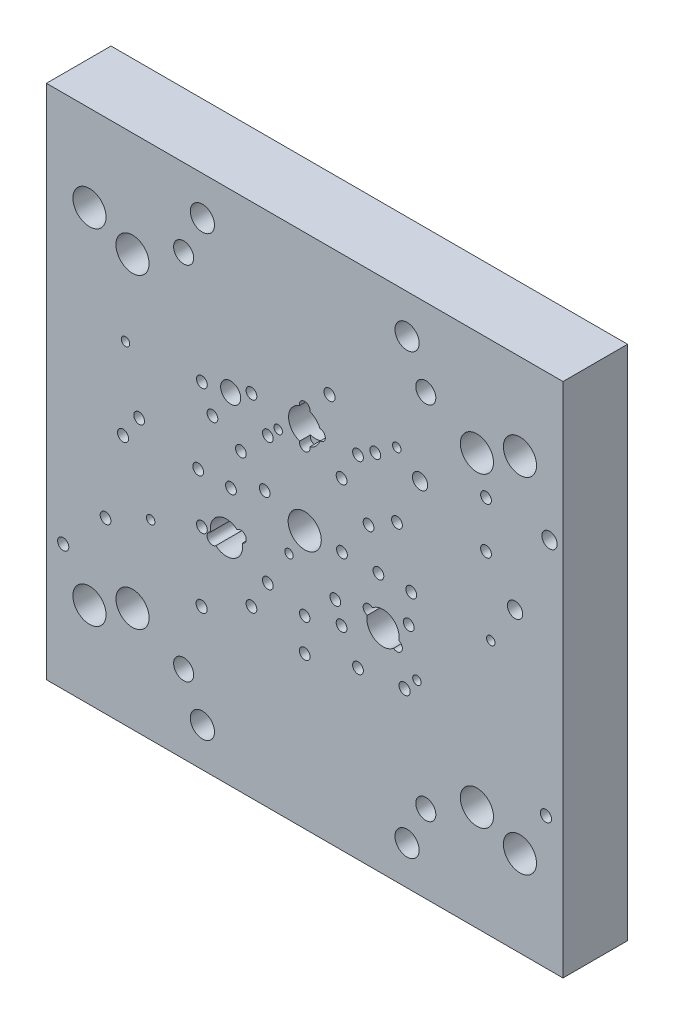
SolidWorks part; units mm, degrees
ref_plane "Front Plane" through (0, 0, 0) normal (0, 0, 1) x (1, 0, 0)
ref_plane "Top Plane" through (0, 0, 0) normal (0, 1, 0) x (1, 0, 0)
ref_plane "Right Plane" through (0, 0, 0) normal (1, 0, 0) x (0, 0, -1)
sketch "Sketch1" plane through (0, 0, 0) normal (0, 0, 1) x (1, 0, 0)
  line L1 (-152.4, 152.4) -> (152.4, 152.4)
  line L2 (-152.4, 152.4) -> (-152.4, -152.4)
  line L3 (-152.4, -152.4) -> (152.4, -152.4)
  line L4 (152.4, 152.4) -> (152.4, -152.4)
  line L5 (-152.4, 152.4) -> (152.4, -152.4) construction
  line L6 (-152.4, -152.4) -> (152.4, 152.4) construction
  point P0 (0, 0)
  dimension "D1" = 304.8
  dimension "D2" = 304.8
extrude "Boss-Extrude1" add sketch "Sketch1" along normal blind 38.1
sketch "Sketch2" plane through (0, 0, 38.1) normal (0, 0, 1) x (1, 0, 0)
  line L0 (-152.4, 0) -> (152.4, 0) construction
  line L5 (-152.4, 152.4) -> (-152.4, -152.4) construction
  line L6 (152.4, -152.4) -> (152.4, 152.4) construction
  line L7 (-152.4, -101.6) -> (152.4, -101.6) construction
  line L8 (-152.4, 101.6) -> (152.4, 101.6) construction
  line L9 (0, 101.6) -> (0, -101.6) construction
  line L10 (127, 101.6) -> (127, -101.6) construction
  line L11 (-127, 101.6) -> (-127, -101.6) construction
  circle A0 centre (-127, 101.6) radius 6.5151
  circle A1 centre (127, 101.6) radius 6.5151
  circle A2 centre (127, -101.6) radius 6.5151
  circle A3 centre (-127, -101.6) radius 6.5151
  circle A4 centre (0, 0) radius 6.5151
  dimension "D5" = 13.0302
  dimension "D1" = 101.6
  dimension "D2" = 101.6
  dimension "D3" = 127
  dimension "D4" = 127
extrude "HAAS T-Slot Holes" cut sketch "Sketch2" against normal through all
sketch "Sketch3" plane through (0, 0, 38.1) normal (0, 0, 1) x (1, 0, 0)
  circle A0 centre (-127, 101.6) radius 9.779
  circle A1 centre (127, 101.6) radius 9.779
  circle A2 centre (0, 0) radius 9.779
  circle A3 centre (127, -101.6) radius 9.779
  circle A4 centre (-127, -101.6) radius 9.779
  dimension "D1" = 19.558
extrude "HAAS Counter Bores" cut sketch "Sketch3" against normal offset from surface (22.225 mm away) 15.875 contours A0 | A1 | A2 | A3 | A4 up to face at (6.5151, 0, 0)
sketch "Sketch4" plane through (0, 0, 38.1) normal (0, 0, 1) x (1, 0, 0)
  line L0 (-127, 90.4875) -> (127, 90.4875) construction
  line L1 (-127, 30.1625) -> (127, 30.1625) construction
  line L2 (-127, 30.1625) -> (-127, -30.1625) construction
  line L3 (-127, -30.1625) -> (127, -30.1625) construction
  line L4 (127, 30.1625) -> (127, -30.1625) construction
  line L5 (-127, 30.1625) -> (127, -30.1625) construction
  line L6 (-127, -30.1625) -> (127, 30.1625) construction
  line L7 (-127, -90.4875) -> (127, -90.4875) construction
  line L8 (-101.6, 90.4875) -> (-101.6, 84.1375) construction
  line L9 (-101.6, -90.4875) -> (-101.6, -84.1375) construction
  line L10 (101.6, -90.4875) -> (101.6, -84.1375) construction
  line L11 (101.6, 90.4875) -> (101.6, 84.1375) construction
  circle A0 centre (-101.6, 90.4875) radius 6.5151
  circle A1 centre (101.6, 90.4875) radius 6.5151
  circle A2 centre (-101.6, -90.4875) radius 6.5151
  circle A3 centre (101.6, -90.4875) radius 6.5151
  point P0 (0, 0)
  dimension "D9" = 13.0302
  dimension "D1" = 60.325
  dimension "D2" = 254
  dimension "D5" = 203.2
  dimension "D6" = 25.4
  dimension "D7" = 203.2
  dimension "D8" = 6.35
  dimension "D3" = 60.325
  dimension "D4" = 60.325
extrude "Tormach T-Slot Holes" cut sketch "Sketch4" against normal through all
sketch "Sketch5" plane through (0, 0, 38.1) normal (0, 0, 1) x (1, 0, 0)
  circle A0 centre (-101.6, 90.4875) radius 9.779
  circle A1 centre (101.6, 90.4875) radius 9.779
  circle A2 centre (101.6, -90.4875) radius 9.779
  circle A3 centre (-101.6, -90.4875) radius 9.779
  dimension "D1" = 19.558
extrude "Tormach Counter bores" cut sketch "Sketch5" against normal up to surface (22.225 mm away) up to face at (-117.221, 101.6, 15.875)
sketch "Sketch6" plane through (0, 0, 38.1) normal (0, 0, 1) x (1, 0, 0)
  circle A0 centre (0, 0) radius 43.5 construction
  circle A1 centre (0, 43.5) radius 3.0734
  circle A2 centre (0, -43.5) radius 3.0734
  dimension "D1" = 87.0001
  dimension "D2" = 6.1468
extrude "Sprocket Locating Holes" cut sketch "Sketch6" against normal blind 6.35
sketch "Sketch7" plane through (0, 0, 38.1) normal (0, 0, 1) x (1, 0, 0)
  circle A0 centre (0, 0) radius 43.5 construction
  circle A2 centre (43.5, 0) radius 3.175
  circle A4 centre (37.6721, -21.75) radius 3.175
  circle A5 centre (21.75, -37.6721) radius 3.175
  circle A6 centre (0, -43.5) radius 3.175 [skipped]
  circle A7 centre (-21.75, -37.6721) radius 3.175
  circle A8 centre (-37.6721, -21.75) radius 3.175
  circle A9 centre (-43.5, 0) radius 3.175
  circle A10 centre (-37.6721, 21.75) radius 3.175
  circle A11 centre (-21.75, 37.6721) radius 3.175
  circle A12 centre (0, 43.5) radius 3.175 [skipped]
  circle A13 centre (21.75, 37.6721) radius 3.175
  circle A14 centre (37.6721, 21.75) radius 3.175
  point P31 (0, 0)
  dimension "D1" = 87.0001
  dimension "D2" = 6.35
  dimension "D3" = 12
extrude "Sprocket Mounting clearance holes" cut sketch "Sketch7" against normal blind 9.525
sketch "Sketch8" plane through (0, 0, 38.1) normal (0, 0, 1) x (1, 0, 0)
  line L1 (-71.4375, 106.4641) -> (71.4375, 106.4641) construction
  line L2 (-71.4375, 106.4641) -> (-71.4375, -106.4641) construction
  line L3 (-71.4375, -106.4641) -> (71.4375, -106.4641) construction
  line L4 (71.4375, 106.4641) -> (71.4375, -106.4641) construction
  line L5 (-71.4375, 106.4641) -> (71.4375, -106.4641) construction
  line L6 (-71.4375, -106.4641) -> (71.4375, 106.4641) construction
  circle A0 centre (-71.4375, 106.4641) radius 5.9182
  circle A1 centre (71.4375, 106.4641) radius 5.9182
  circle A2 centre (71.4375, -106.4641) radius 5.9182
  circle A3 centre (-71.4375, -106.4641) radius 5.9182
  point P0 (0, 0)
  dimension "D3" = 11.8364
  dimension "D1" = 142.875
  dimension "D2" = 212.9282
extrude "1/2-13 Tapped Holes" cut sketch "Sketch8" against normal blind 19.05
sketch "Sketch9" plane through (0, 0, 38.1) normal (0, 0, 1) x (1, 0, 0)
  circle A0 centre (-117.5189, -52.2876) radius 3.175
  circle A1 centre (-60.6634, -28.4101) radius 3.175
  circle A2 centre (-60.6634, 45.677) radius 3.175
  circle A3 centre (-23.6198, 8.6335) radius 3.175
  circle A4 centre (-97.707, 8.6335) radius 3.175
  circle A5 centre (18.0623, -26.1797) radius 3.175
  circle A6 centre (21.9762, 0) radius 3.175
  circle A7 centre (61.3833, -17.3739) radius 3.175
  circle A8 centre (106.976, 70.3959) radius 3.175
  circle A9 centre (106.976, 42.9004) radius 3.175
  circle A10 centre (144.4539, 67.4373) radius 4.5
  circle A11 centre (124.1092, 21.6131) radius 4.5
  circle A12 centre (68.0681, 59.3279) radius 4.5
  circle A13 centre (58.9353, -51.2652) radius 3.3
  circle A14 centre (-142.4923, -78.095) radius 3.3
  circle A15 centre (-105.7351, 43.7713) radius 2.5
  circle A16 centre (-90.8975, -39.8642) radius 2.5
  circle A17 centre (-9.2711, -16.3656) radius 2.5
  circle A18 centre (-15.6655, 43.8657) radius 2.5
  circle A20 centre (14.6267, 76.8405) radius 3.3
  circle A21 centre (8.9855, 53.4682) radius 3.175
  circle A22 centre (41.6559, 60.6579) radius 3.175
extrude "SSB Holes" cut sketch "Sketch9" against normal blind 19.05
ref_axis "Axis1" through (0, 0, 0) along (0, 0, 1)
sketch "Sketch10" plane through (0, 0, 38.1) normal (0, 0, 1) x (1, 0, 0)
  circle A0 centre (0, 0) radius 62.865 construction
  circle A1 centre (0, 62.865) radius 3.175
  circle A13 centre (31.4325, 54.4427) radius 3.175
  circle A14 centre (54.4427, 31.4325) radius 3.175
  circle A15 centre (62.865, 0) radius 3.175
  circle A16 centre (54.4427, -31.4325) radius 3.175
  circle A17 centre (31.4325, -54.4427) radius 3.175
  circle A18 centre (0, -62.865) radius 3.175
  circle A19 centre (-31.4325, -54.4427) radius 3.175
  circle A20 centre (-54.4427, -31.4325) radius 3.175
  circle A21 centre (-62.865, 0) radius 3.175
  circle A22 centre (-54.4427, 31.4325) radius 3.175
  circle A23 centre (-31.4325, 54.4427) radius 3.175
  point P30 (0, 0)
  point P56 (0, 0)
  dimension "D1" = 125.73
  dimension "D2" = 6.35
  dimension "D4" = 12
extrude "Sprocket Countersunk Holes" cut sketch "Sketch10" against normal blind 19.05
sketch "Sketch12" plane through (0, 0, 38.1) normal (0, 0, 1) x (1, 0, 0)
  circle A0 centre (-107.2144, -4.9977) radius 3.3
  circle A1 centre (-60.8212, -69.1392) radius 3.3
  circle A2 centre (142.3129, -74.567) radius 3.3
  circle A4 centre (54.3307, 69.7186) radius 2.4964
  circle A5 centre (109.7823, -1.2607) radius 2.5
  circle A6 centre (66.2094, -43.3332) radius 2.5
  circle A7 centre (-43.6886, 48.7489) radius 5.9182
  circle A8 centre (-71.4375, 106.4641) radius 5.9182 construction
extrude "DSB Holes" cut sketch "Sketch12" against normal blind 19.05
sketch "Brake Rotor Toe Clamp Holes" plane through (0, 0, 38.1) normal (0, 0, 1) x (1, 0, 0)
  line L0 (-55.0143, 117.9786) -> (55.0143, -117.9786) construction
  line L1 (55.0143, 117.9786) -> (-55.0143, -117.9786) construction
  line L2 (-55.0143, 117.9786) -> (-60.3816, 129.4887) construction
  line L3 (55.0143, 117.9786) -> (60.3816, 129.4887) construction
  line L4 (-55.0143, -117.9786) -> (-60.3816, -129.4887) construction
  line L5 (55.0143, -117.9786) -> (60.3816, -129.4887) construction
  line L6 (0, 0) -> (192.0367, 0) construction
  line L7 (0, 0) -> (-160.9096, 0) construction
  line L8 (0, 0) -> (0, 219.8313) construction
  circle A0 centre (0, 0) radius 130.175 construction
  circle A6 centre (-60.3816, 129.4887) radius 7.1437
  circle A7 centre (60.3816, 129.4887) radius 7.1437
  circle A8 centre (60.3816, -129.4887) radius 7.1437
  circle A9 centre (-60.3816, -129.4887) radius 7.1437
  circle A11 centre (0, 53.34) radius 9.525
  circle A13 centre (46.1938, -26.67) radius 9.525
  circle A14 centre (-46.1938, -26.67) radius 9.525
  point P27 (0, 0)
  dimension "D1" = 260.35
  dimension "D2" = 14.2875
  dimension "D3" = 14.2875
  dimension "D4" = 14.2875
  dimension "D5" = 14.2875
  dimension "D17" = 19.05
  dimension "D6" = 12.7
  dimension "D7" = 12.7
  dimension "D8" = 12.7
  dimension "D9" = 12.7
  dimension "D10" = 65
  dimension "D11" = 65
  dimension "D12" = 3
  dimension "D16" = 53.34
extrude "Brake Rotor Holes" cut sketch "Brake Rotor Toe Clamp Holes" against normal through all
